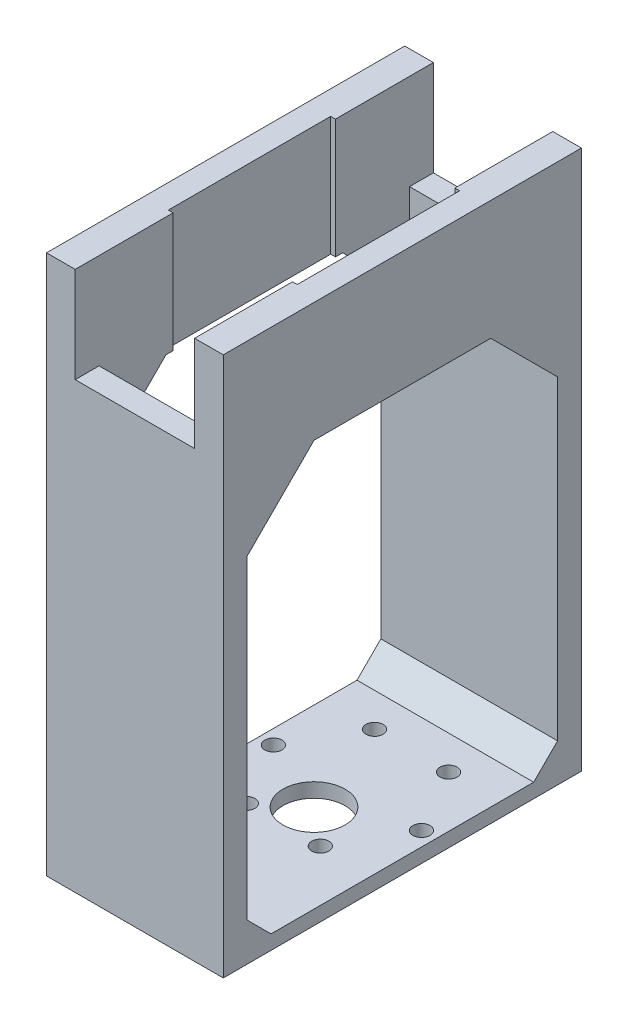
SolidWorks part; units mm, degrees
ref_plane "Front Plane" through (0, 0, 0) normal (0, 0, 1) x (1, 0, 0)
ref_plane "Top Plane" through (0, 0, 0) normal (0, 1, 0) x (1, 0, 0)
ref_plane "Right Plane" through (0, 0, 0) normal (1, 0, 0) x (0, 0, -1)
sketch "Sketch2" plane through (0, 0, 0) normal (0, 1, 0) x (1, 0, 0)
  line L1 (7.75, -13.4234) -> (15.5, 0) construction
  line L2 (15.5, 0) -> (7.75, 13.4234) construction
  line L3 (7.75, 13.4234) -> (-7.75, 13.4234) construction
  line L4 (-7.75, 13.4234) -> (-15.5, 0) construction
  line L5 (-15.5, 0) -> (-7.75, -13.4234) construction
  line L6 (-7.75, -13.4234) -> (7.75, -13.4234) construction
  circle A0 centre (0, 0) radius 13.4234 construction
  circle A1 centre (-15.5, 0) radius 1.8
  circle A2 centre (-7.75, 13.4234) radius 1.8
  circle A3 centre (7.75, 13.4234) radius 1.8
  circle A4 centre (15.5, 0) radius 1.8
  circle A5 centre (7.75, -13.4234) radius 1.8
  circle A6 centre (-7.75, -13.4234) radius 1.8
  circle A7 centre (0, 0) radius 18.5
  dimension "D2" = 3.6
  dimension "D3" = 37
  dimension "D1" = 31
extrude "Boss-Extrude1" add sketch "Sketch2" along normal blind 3
sketch "Sketch3" plane through (0, 3, 0) normal (0, 1, 0) x (1, 0, 0)
  line L0 (0, 0) -> (0, -7) construction
  circle A0 centre (0, -7) radius 6.5
  dimension "D2" = 13
  dimension "D1" = 7
extrude "Cut-Extrude1" cut sketch "Sketch3" against normal blind 3
sketch "Sketch4" plane through (0, 3, 0) normal (0, 1, 0) x (1, 0, 0)
  line L1 (-18.5, 30.5) -> (18.5, 30.5)
  line L4 (-18.5, -44.5) -> (18.5, -44.5)
  line L6 (-18.5, -44.5) -> (-18.5, 30.5)
  line L7 (18.5, 30.5) -> (18.5, -44.5)
  line L8 (0, -7) -> (2.9813, -7) construction
  circle A1 centre (0, 0) radius 18.5
  circle A2 centre (0, 0) radius 18.5
  point P7 (18.5, -7)
  circle M11 centre (0, 0) radius 18.5
  dimension "D2" = 75
  dimension "D1" = 0
extrude "Boss-Extrude2" add sketch "Sketch4" against normal up to surface (3 mm away) contours L7 L1 L6 M11 | L7 L6 L4 M11 region at (0, 3, -21.9811) region at (0, 3, 29.2305) up to face at (0, 0, 13.5)
sketch "Sketch5" plane through (0, 3, 0) normal (0, 1, 0) x (1, 0, 0)
  line L0 (18.5, 30.5) -> (18.5, -44.5) construction
  line L1 (-18.5, 30.5) -> (18.5, 30.5)
  line L2 (-18.5, 30.5) -> (-18.5, 25.5)
  line L3 (-18.5, 25.5) -> (18.5, 25.5)
  line L4 (18.5, 30.5) -> (18.5, 25.5)
  line L6 (-18.5, -44.5) -> (18.5, -44.5)
  line L7 (-18.5, -44.5) -> (-18.5, -39.5)
  line L8 (-18.5, -39.5) -> (18.5, -39.5)
  line L9 (18.5, -44.5) -> (18.5, -39.5)
  dimension "D1" = 5
extrude "Boss-Extrude3" add sketch "Sketch5" along normal blind 90
sketch "Sketch6" plane through (0, 93, 0) normal (0, 1, 0) x (1, 0, 0)
  line L0 (18.5, 25.5) -> (18.5, -39.5) construction
  line L1 (-18.5, 25.5) -> (18.5, 25.5)
  line L2 (-18.5, 25.5) -> (-18.5, 10)
  line L3 (-18.5, 10) -> (18.5, 10)
  line L4 (18.5, 25.5) -> (18.5, 10)
  line L6 (-18.5, -39.5) -> (18.5, -39.5)
  line L7 (-18.5, -39.5) -> (-18.5, -24)
  line L8 (-18.5, -24) -> (18.5, -24)
  line L9 (18.5, -39.5) -> (18.5, -24)
  dimension "D1" = 34
extrude "Boss-Extrude4" add sketch "Sketch6" against normal blind 5
sketch "Sketch7" plane through (0, 93, 0) normal (0, 1, 0) x (1, 0, 0)
  line L0 (18.5, 30.5) -> (-18.5, 30.5) construction
  line L1 (-18.5, 10) -> (-12.5, 10)
  line L2 (-18.5, 10) -> (-18.5, 30.5)
  line L3 (-18.5, 30.5) -> (-12.5, 30.5)
  line L4 (-12.5, 10) -> (-12.5, 30.5)
  line L5 (18.5, 10) -> (12.5, 10)
  line L6 (18.5, 10) -> (18.5, 30.5)
  line L7 (18.5, 30.5) -> (12.5, 30.5)
  line L8 (12.5, 10) -> (12.5, 30.5)
  line L9 (-18.5, -24) -> (-12.5, -24)
  line L10 (-18.5, -24) -> (-18.5, -44.5)
  line L11 (-18.5, -44.5) -> (-12.5, -44.5)
  line L12 (-12.5, -24) -> (-12.5, -44.5)
  line L13 (18.5, -24) -> (12.5, -24)
  line L14 (18.5, -24) -> (18.5, -44.5)
  line L15 (18.5, -44.5) -> (12.5, -44.5)
  line L16 (12.5, -24) -> (12.5, -44.5)
  dimension "D1" = 25
extrude "Boss-Extrude5" add sketch "Sketch7" along normal blind 20
sketch "Sketch8" plane through (0, 93, 0) normal (0, 1, 0) x (1, 0, 0)
  line L0 (-12.5, 10) -> (-12.5, 25.5)
  line L1 (-12.5, 10) -> (-12.5, 30.5) construction
  line L2 (-12.5, 25.5) -> (12.5, 25.5)
  line L3 (12.5, 30.5) -> (12.5, 10) construction
  line L4 (12.5, 25.5) -> (12.5, 10)
  line L5 (12.5, 10) -> (-12.5, 10)
  line L6 (-12.5, -24) -> (12.5, -24)
  line L7 (12.5, -24) -> (12.5, -39.5)
  line L8 (12.5, -24) -> (12.5, -44.5) construction
  line L9 (12.5, -39.5) -> (-12.5, -39.5)
  line L10 (-12.5, -44.5) -> (-12.5, -24) construction
  line L11 (-12.5, -39.5) -> (-12.5, -24)
  line L12 (-18.5, 25.5) -> (18.5, 25.5) construction
  line L13 (18.5, -39.5) -> (-18.5, -39.5) construction
extrude "Cut-Extrude2" cut sketch "Sketch8" against normal blind 10
sketch "Sketch9" plane through (0, 93, 0) normal (0, 1, 0) x (1, 0, 0)
  line L0 (12.5, 30.5) -> (12.5, 10) construction
  line L1 (-12.5, 30.5) -> (12.5, 30.5)
  line L2 (-12.5, 30.5) -> (-12.5, 25.5)
  line L3 (-12.5, 25.5) -> (12.5, 25.5)
  line L4 (12.5, 30.5) -> (12.5, 25.5)
  line L5 (-18.5, 25.5) -> (18.5, 25.5) construction
  line L7 (-12.5, -39.5) -> (12.5, -39.5)
  line L8 (-12.5, -39.5) -> (-12.5, -44.5)
  line L9 (-12.5, -44.5) -> (12.5, -44.5)
  line L10 (12.5, -39.5) -> (12.5, -44.5)
extrude "Boss-Extrude6" add sketch "Sketch9" along normal up to surface (20 mm away) up to face at (-15.5, 113, -20.25)
sketch "Sketch10" plane through (0, 0, 24) normal (0, 0, -1) x (-1, 0, 0)
  line L0 (12.5, 88) -> (18.5, 88) construction
  line L1 (18.5, 113) -> (13.5, 113)
  line L2 (18.5, 113) -> (18.5, 88)
  line L3 (18.5, 88) -> (13.5, 88)
  line L4 (13.5, 113) -> (13.5, 88)
  line L5 (-18.5, 88) -> (-12.5, 88) construction
  line L6 (-18.5, 113) -> (-13.5, 113)
  line L7 (-18.5, 113) -> (-18.5, 88)
  line L8 (-18.5, 88) -> (-13.5, 88)
  line L9 (-13.5, 113) -> (-13.5, 88)
  dimension "D1" = 5
extrude "Boss-Extrude7" add sketch "Sketch10" along normal up to next
sketch "Sketch11" plane through (0, 0, 44.5) normal (0, 0, 1) x (1, 0, 0)
  line L0 (-18.5, 113) -> (18.5, 113) construction
  line L1 (-12.5, 113) -> (12.5, 113)
  line L2 (-12.5, 113) -> (-12.5, 93)
  line L3 (-12.5, 93) -> (12.5, 93)
  line L4 (12.5, 113) -> (12.5, 93)
  line L7 (0, 93) -> (0, 113) construction
  line L8 (-18.5, 0) -> (-18.5, 113) construction
  line L9 (18.5, 0) -> (18.5, 113) construction
  line L10 (-12.5, 113) -> (-12.5, 88) construction
  dimension "D1" = 20
extrude "Cut-Extrude3" cut sketch "Sketch11" against normal through all
ref_plane "Plane1" through (12.5, 88, 39.5) normal (1, 0, 0) x (0, 0, -1)
chamfer "Chamfer1" distance 14 angle 45 2 edges at (-15.5, 88, -25.5) (-15.5, 88, 39.5)
chamfer "Chamfer2" distance 5 angle 45 2 edges at (0, 3, -25.5) (0, 3, 39.5)
